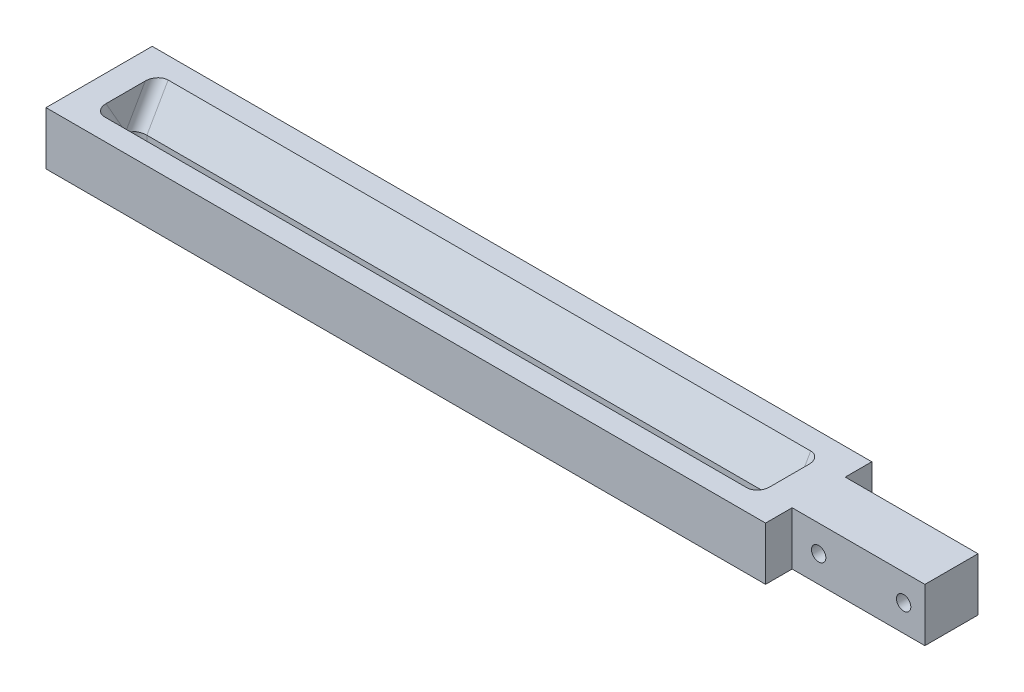
SolidWorks part; units mm, degrees
material "PLA"
ref_plane "前视基准面" through (0, 0, 0) normal (0, 0, 1) x (1, 0, 0)
ref_plane "上视基准面" through (0, 0, 0) normal (0, 1, 0) x (1, 0, 0)
ref_plane "右视基准面" through (0, 0, 0) normal (1, 0, 0) x (0, 0, -1)
sketch "草图1" plane through (0, 0, 0) normal (0, 1, 0) x (1, 0, 0)
  line L0 (-67.5, -10) -> (-67.5, 10)
  line L5 (-67.5, 10) -> (67.5, 10)
  line L6 (67.5, -10) -> (67.5, 10)
  line L7 (-62.5, -5) -> (62.5, -5) construction
  line L8 (-62.5, -5) -> (-62.5, 5) construction
  line L9 (-62.5, 5) -> (62.5, 5) construction
  line L10 (62.5, -5) -> (62.5, 5) construction
  line L11 (0, 5) -> (0, -5) construction
  line L12 (-62.5, 0) -> (62.5, 0) construction
  line L13 (-67.5, -10) -> (67.5, -10)
  point P0 (0, 0)
  point P4 (0, 0)
  dimension "D1" = 125
  dimension "D2" = 10
  dimension "D3" = 5
extrude "凸台-拉伸3" add sketch "草图1" along normal blind 10
sketch "草图2" plane through (0, 0, 0) normal (1, 0, 0) x (0, 0, -1)
  line L0 (-6, 10) -> (-2, 3)
  line L1 (-10, 10) -> (10, 10) construction
  line L2 (-3.15, 5.0125) -> (3.15, 5.0125) construction
  line L4 (6, 10) -> (-6, 10)
  line L6 (0, 10) -> (0, 0) construction
  line L7 (6, 10) -> (2, 3)
  line L10 (-2, 3) -> (-2, 0)
  line L11 (-10, 0) -> (10, 0) construction
  line L12 (-2, 0) -> (2, 0)
  line L13 (2, 0) -> (2, 3)
  dimension "D1" = 4
  dimension "D2" = 12
  dimension "D3" = 3
  dimension "D4" = 6.3
  dimension "D5" = 5.0125
extrude "切除-拉伸1" cut sketch "草图2" against normal mid plane 125
ref_plane "基准面1" through (0, 4.58, 0) normal (0, -1, 0) x (-1, 0, 0)
fillet "圆角1" radius 2 8 edges at (62.5, 6.5, 4) (62.5, 6.5, -4) (-62.5, 6.5, -4) (-62.5, 6.5, 4) (-62.5, 1.5, -2) (62.5, 1.5, -2) (62.5, 1.5, 2) (-62.5, 1.5, 2)
ref_plane "令牌下檐面" through (0, 5.01, 0) normal (0, -1, 0) x (-1, 0, 0)
sketch "草图4" plane through (0, 10, 0) normal (0, 1, 0) x (1, 0, 0)
  line L0 (67.5, 10) -> (-67.5, 10) construction
  line L1 (67.5, -10) -> (93, -10)
  line L2 (67.5, -10) -> (67.5, 10)
  line L3 (67.5, 10) -> (93, 10)
  line L4 (93, -10) -> (93, 10)
  dimension "D1" = 25.5
extrude "凸台-拉伸5" add sketch "草图4" against normal up to surface (10 mm away) up to face at (0, 0, 0)
sketch "草图5" plane through (0, 0, -10) normal (0, 0, -1) x (-1, 0, 0)
  line L0 (-93, 5) -> (67.5, 5) construction
  line L1 (-93, 0) -> (-93, 10) construction
  line L2 (67.5, 10) -> (67.5, 0) construction
  circle A0 centre (-89, 5) radius 1.35
  circle A1 centre (-73, 5) radius 1.35
  dimension "D3" = 2.7
  dimension "D1" = 4
  dimension "D2" = 16
extrude "切除-拉伸2" cut sketch "草图5" against normal through all
sketch "草图6" plane through (0, 10, 0) normal (0, 1, 0) x (1, 0, 0)
  line L0 (93, 0) -> (62.5, 0) construction
  line L1 (93, -10) -> (93, 10) construction
  line L2 (93, -5) -> (68, -5)
  line L3 (93, 10) -> (68, 10)
  line L4 (93, 10) -> (93, 5)
  line L5 (93, 5) -> (68, 5)
  line L6 (68, 10) -> (68, 5)
  line L7 (68, -10) -> (68, -5)
  line L8 (93, -10) -> (68, -10)
  line L9 (93, -10) -> (93, -5)
  dimension "D1" = 5
  dimension "D2" = 25
extrude "切除-拉伸3" cut sketch "草图6" against normal through all
